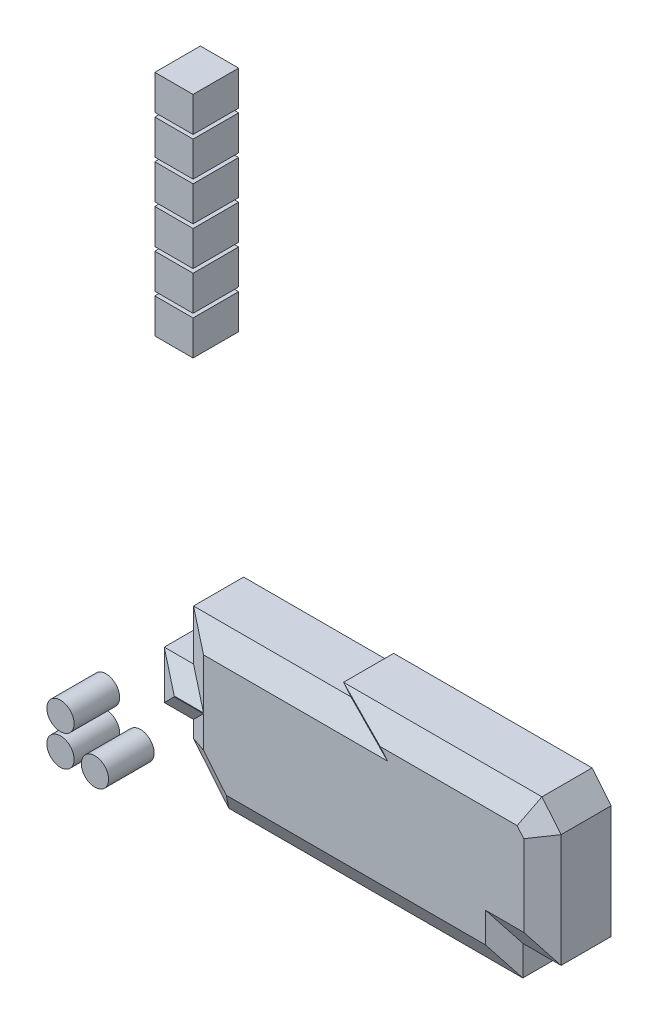
SolidWorks part; units mm, degrees
ref_plane "Спереди" through (0, 0, 0) normal (0, 0, 1) x (1, 0, 0)
ref_plane "Сверху" through (0, 0, 0) normal (0, 1, 0) x (1, 0, 0)
ref_plane "Справа" through (0, 0, 0) normal (1, 0, 0) x (0, 0, -1)
sketch "Эскиз1" plane through (0, 0, 0) normal (0, 0, 1) x (1, 0, 0)
  line L0 (-36.9099, -38.2911) -> (-36.9099, -49.3242)
  line L1 (-36.9099, -49.3242) -> (-43.3321, -49.3242)
  line L2 (-43.3321, -49.3242) -> (-43.3321, -59.8632)
  line L3 (-43.3321, -59.8632) -> (-36.9099, -59.8632)
  line L4 (-36.9099, -59.8632) -> (-36.9099, -63.486)
  line L5 (-36.9099, -63.486) -> (-29.1703, -72.8723)
  line L6 (-29.1703, -72.8723) -> (35.3814, -72.8723)
  line L7 (35.3814, -72.8723) -> (35.3814, -66.2854)
  line L8 (35.3814, -66.2854) -> (43.7797, -66.2854)
  line L9 (43.7797, -66.2854) -> (43.7797, -41.4199)
  line L10 (43.7797, -41.4199) -> (39.5806, -36.3273)
  line L11 (39.5806, -36.3273) -> (-3.9727, -36.3273)
  line L12 (-3.9727, -36.3273) -> (-2.3534, -38.2911)
  line L13 (-2.3534, -38.2911) -> (-36.9099, -38.2911)
extrude "Бобышка-Вытянуть1" add sketch "Эскиз1" along normal blind 14
chamfer "Фаска1" distance 3 angle 60 14 edges at (-3.1631, -37.3092, 14) (17.8039, -36.3273, 14) (41.6801, -38.8736, 14) (43.7797, -53.8527, 14) (39.5806, -66.2854, 14) (35.3814, -69.5789, 14) (3.1056, -72.8723, 14) (-33.0401, -68.1792, 14) (-36.9099, -61.6746, 14) (-40.121, -59.8632, 14) (-43.3321, -54.5937, 14) (-40.121, -49.3242, 14) (-36.9099, -43.8076, 14) (-19.6317, -38.2911, 14) first distance on face at (-3.1631, -37.3092, 7) first distance on face at (17.8039, -36.3273, 7) first distance on face at (41.6801, -38.8736, 7) first distance on face at (43.7797, -53.8527, 7) first distance on face at (39.5806, -66.2854, 7) first distance on face at (35.3814, -69.5789, 7) first distance on face at (3.1056, -72.8723, 7) first distance on face at (-33.0401, -68.1792, 7) first distance on face at (-36.9099, -61.6746, 7) first distance on face at (-40.121, -59.8632, 7) first distance on face at (-43.3321, -54.5937, 7) first distance on face at (-40.121, -49.3242, 7) first distance on face at (-36.9099, -43.8076, 7) first distance on face at (-19.6317, -38.2911, 7)
sketch "Эскиз2" plane through (0, 0, 0) normal (0, 0, 1) x (1, 0, 0)
  line L0 (-46.4076, 49.4192) -> (-46.4076, 41.7952)
  line L1 (-46.4076, 57.9192) -> (-38.0083, 57.9192)
  line L2 (-46.4076, 57.9192) -> (-46.4076, 50.2952)
  line L3 (-46.4076, 50.2952) -> (-38.0083, 50.2952)
  line L4 (-38.0083, 57.9192) -> (-38.0083, 50.2952)
  line L5 (-46.4076, 49.4192) -> (-38.0083, 49.4192)
  line L6 (-38.0083, 49.4192) -> (-38.0083, 41.7952)
  line L7 (-46.4076, 41.7952) -> (-38.0083, 41.7952)
  line L8 (-46.4076, 40.9192) -> (-46.4076, 33.2952)
  line L9 (-46.4076, 40.9192) -> (-38.0083, 40.9192)
  line L10 (-38.0083, 40.9192) -> (-38.0083, 33.2952)
  line L11 (-46.4076, 33.2952) -> (-38.0083, 33.2952)
  line L12 (-46.4076, 32.4192) -> (-46.4076, 24.7952)
  line L13 (-46.4076, 32.4192) -> (-38.0083, 32.4192)
  line L14 (-38.0083, 32.4192) -> (-38.0083, 24.7952)
  line L15 (-46.4076, 24.7952) -> (-38.0083, 24.7952)
  line L16 (-46.4076, 23.9192) -> (-46.4076, 16.2952)
  line L17 (-46.4076, 23.9192) -> (-38.0083, 23.9192)
  line L18 (-38.0083, 23.9192) -> (-38.0083, 16.2952)
  line L19 (-46.4076, 16.2952) -> (-38.0083, 16.2952)
  line L20 (-46.4076, 15.4192) -> (-46.4076, 7.7952)
  line L21 (-46.4076, 15.4192) -> (-38.0083, 15.4192)
  line L22 (-38.0083, 15.4192) -> (-38.0083, 7.7952)
  line L23 (-46.4076, 7.7952) -> (-38.0083, 7.7952)
  line L24 (-46.4076, 57.9192) -> (-46.4076, 49.4192) construction
  circle A0 centre (-67.1232, -74.7902) radius 3
  circle A1 centre (-67.1232, -81.5853) radius 3
  circle A2 centre (-59.5559, -81.5853) radius 3
  dimension "D1" = 6
  dimension "D2" = 8.5
extrude "Бобышка-Вытянуть2" add sketch "Эскиз2" along normal blind 10 separate body
